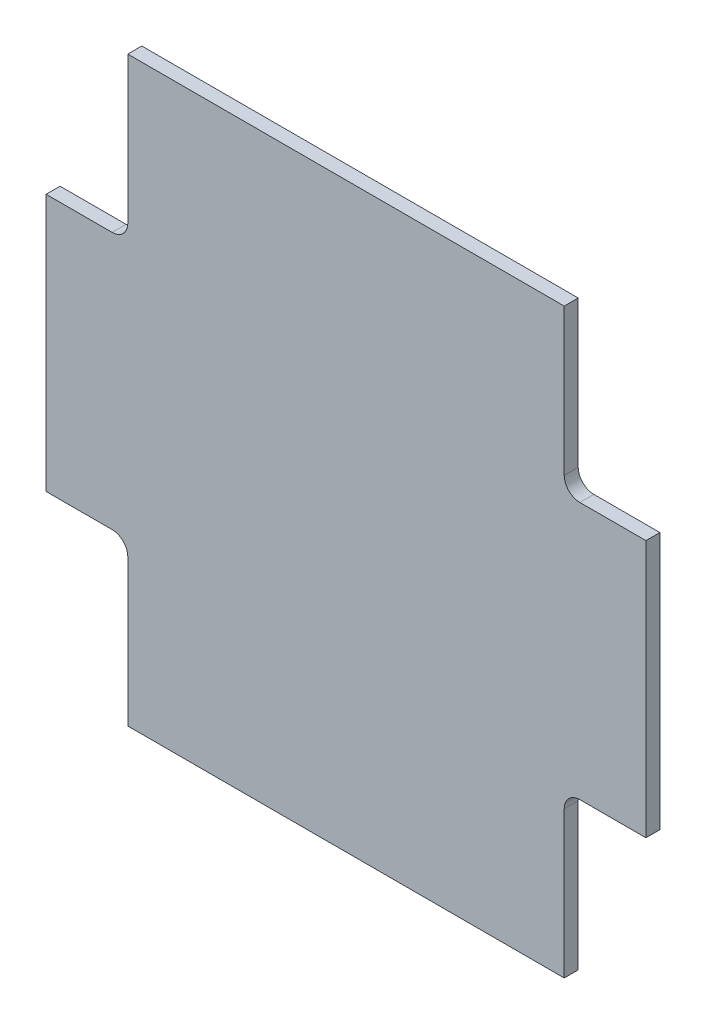
SolidWorks part; units mm, degrees
ref_plane "Front Plane" through (0, 0, 0) normal (0, 0, 1) x (1, 0, 0)
ref_plane "Top Plane" through (0, 0, 0) normal (0, 1, 0) x (1, 0, 0)
ref_plane "Right Plane" through (0, 0, 0) normal (1, 0, 0) x (0, 0, -1)
sketch "Sketch1" plane through (0, 0, 0) normal (0, 0, 1) x (1, 0, 0)
  line L0 (0, 47.625) -> (0, 18.415)
  line L1 (0, 18.415) -> (7.493, 18.415)
  line L2 (9.271, 16.637) -> (9.271, 0)
  line L3 (9.271, 0) -> (58.801, 0)
  line L4 (0, 33.02) -> (34.036, 33.02) construction
  line L5 (34.036, 33.02) -> (34.036, 0) construction
  line L6 (58.801, 16.637) -> (58.801, 0)
  line L7 (68.072, 18.415) -> (60.579, 18.415)
  line L8 (68.072, 47.625) -> (68.072, 18.415)
  line L9 (9.271, 49.403) -> (9.271, 66.04)
  line L10 (0, 47.625) -> (7.493, 47.625)
  line L11 (9.271, 66.04) -> (58.801, 66.04)
  line L12 (68.072, 47.625) -> (60.579, 47.625)
  line L13 (58.801, 49.403) -> (58.801, 66.04)
  arc A0 (9.271, 16.637) -> (7.493, 18.415) centre (7.493, 16.637) ccw
  arc A1 (58.801, 16.637) -> (60.579, 18.415) centre (60.579, 16.637) cw
  arc A2 (9.271, 49.403) -> (7.493, 47.625) centre (7.493, 49.403) cw
  arc A3 (58.801, 49.403) -> (60.579, 47.625) centre (60.579, 49.403) ccw
  point P21 (68.072, 33.02)
  dimension "D5" = 1.778
  dimension "D1" = 24.765
  dimension "D2" = 34.036
  dimension "D3" = 33.02
  dimension "D4" = 14.605
extrude "Boss-Extrude1" add sketch "Sketch1" along normal blind 1.5875
